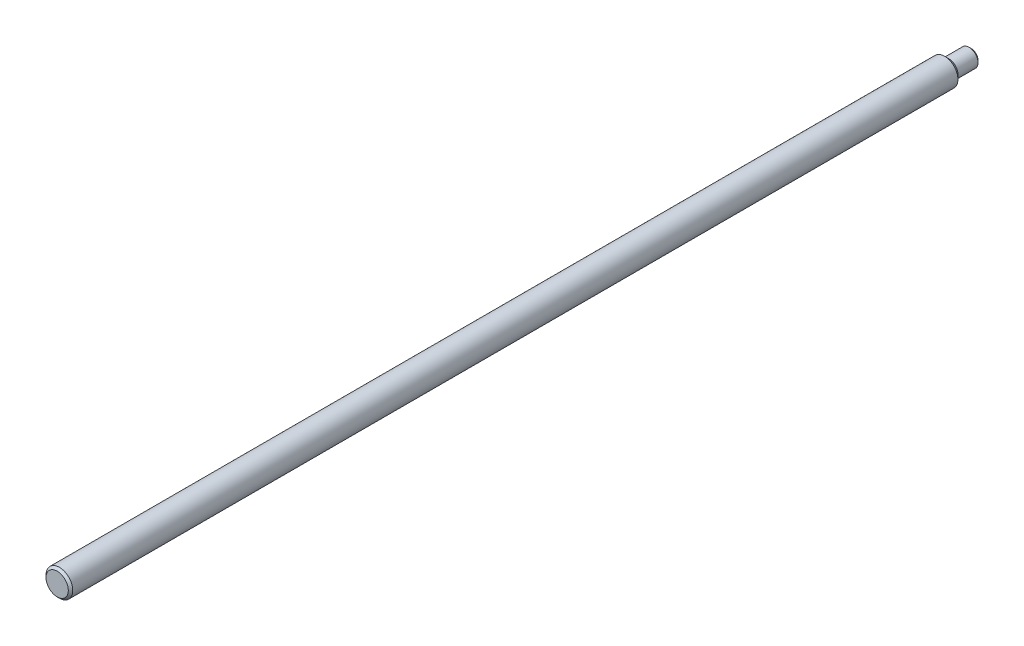
SolidWorks part; units mm, degrees
ref_plane "Piano frontale" through (0, 0, 0) normal (0, 0, 1) x (1, 0, 0)
ref_plane "Piano superiore" through (0, 0, 0) normal (0, 1, 0) x (1, 0, 0)
ref_plane "Piano destro" through (0, 0, 0) normal (1, 0, 0) x (0, 0, -1)
sketch "Schizzo1" plane through (0, 0, 0) normal (0, 0, 1) x (1, 0, 0)
  circle A0 centre (0, 0) radius 6
  dimension "D1" = 12
extrude "Estrusione-Estrusione1" add sketch "Schizzo1" along normal blind 410
cosmetic thread "Filettatura cosmetica1" parameters "D2"=10.344
sketch "Schizzo2" plane through (0, 0, 0) normal (0, 1, 0) x (1, 0, 0)
  line L0 (0, 1.8987) -> (0, -61.2971) construction
  line L1 (-4, -10) -> (-6, -12)
  line L2 (-6, -12) -> (-6, 0)
  line L3 (-6, 0) -> (-4, 0)
  line L4 (-4, 0) -> (-4, -10)
  line L5 (-6, 0) -> (-6, -410) construction
  line L6 (6, 0) -> (-6, 0) construction
  dimension "D1" = 8
  dimension "D2" = 135
  dimension "D3" = 10
revolve "Taglia-Rivoluzione1" cut sketch "Schizzo2" angle 360 about L0
chamfer "Smusso1" distance 1 angle 45 2 edges at (-4, 0, 0) (6, 0, 410)
sketch "Schizzo3" plane through (0, 0, 0) normal (0, 1, 0) x (1, 0, 0)
  line L0 (-4, -10) -> (-4, -10.2926)
